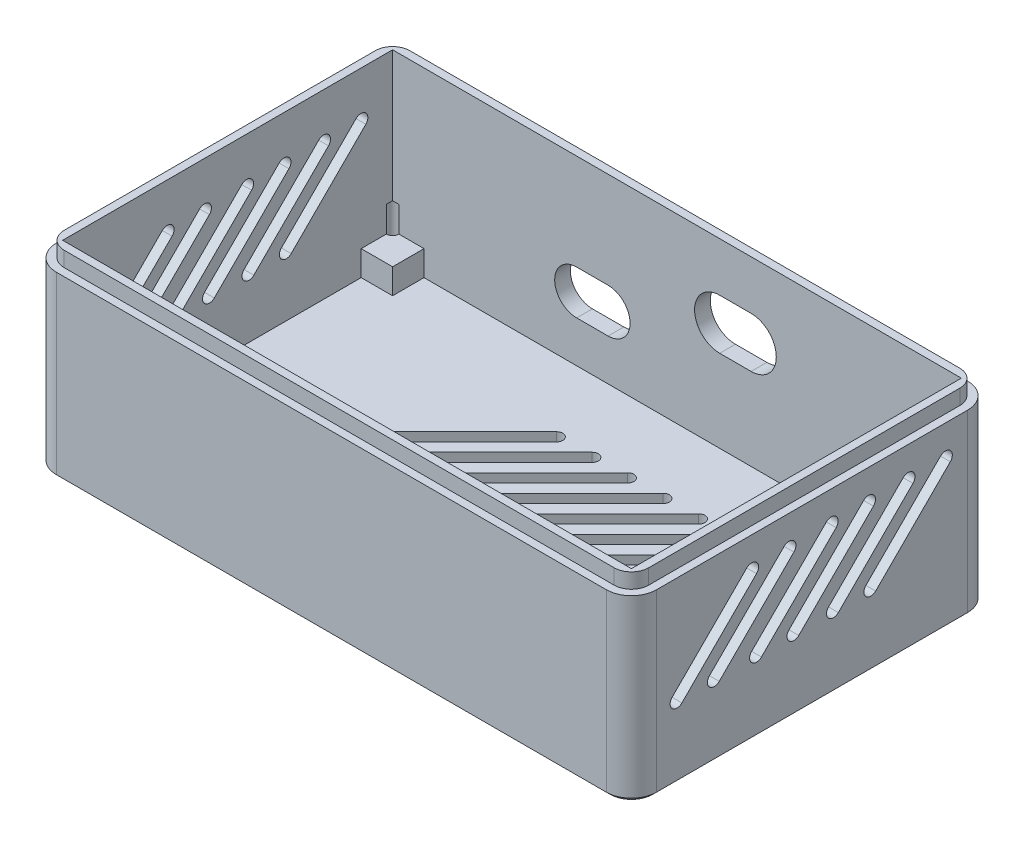
SolidWorks part; units mm, degrees
ref_plane "Front Plane" through (0, 0, 0) normal (0, 0, 1) x (1, 0, 0)
ref_plane "Top Plane" through (0, 0, 0) normal (0, 1, 0) x (1, 0, 0)
ref_plane "Right Plane" through (0, 0, 0) normal (1, 0, 0) x (0, 0, -1)
sketch "Croquis_contorno" plane through (0, 0, 0) normal (0, 1, 0) x (1, 0, 0)
  line L0 (-43.75, -28.75) -> (43.75, -28.75)
  line L1 (47.75, -24.75) -> (47.75, 24.75)
  line L2 (43.75, 28.75) -> (-43.75, 28.75)
  line L3 (-47.75, 24.75) -> (-47.75, -24.75)
  arc A0 (43.75, -28.75) -> (47.75, -24.75) centre (43.75, -24.75) ccw
  arc A1 (47.75, 24.75) -> (43.75, 28.75) centre (43.75, 24.75) ccw
  arc A2 (-43.75, 28.75) -> (-47.75, 24.75) centre (-43.75, 24.75) ccw
  arc A3 (-47.75, -24.75) -> (-43.75, -28.75) centre (-43.75, -24.75) ccw
  dimension "D3" = 4
  dimension "D1" = 95.5
  dimension "D2" = 57.5
extrude "Cuerpo" add sketch "Croquis_contorno" along normal blind 28.5
ref_plane "Plano_Top Plane_+28_5" through (0, 28.5, 0) normal (0, 1, 0) x (1, 0, 0)
sketch "Croquis_hueco_PCB" plane through (0, 28.5, 0) normal (0, 1, 0) x (1, 0, 0)
  line L1 (-45.25, -26.25) -> (45.25, -26.25)
  line L2 (-45.25, -26.25) -> (-45.25, 26.25)
  line L3 (-45.25, 26.25) -> (45.25, 26.25)
  line L4 (45.25, -26.25) -> (45.25, 26.25)
  line L5 (-45.25, -26.25) -> (45.25, 26.25) construction
  line L6 (-45.25, 26.25) -> (45.25, -26.25) construction
  dimension "D1" = 90.5
  dimension "D2" = 52.5
extrude "Hueco_PCB" cut sketch "Croquis_hueco_PCB" against normal blind 26.5
sketch "Croquis_labio" plane through (0, 28.5, 0) normal (0, 1, 0) x (1, 0, 0)
  line L0 (-43.75, -27.5) -> (43.75, -27.5)
  line L1 (46.5, -24.75) -> (46.5, 24.75)
  line L2 (43.75, 27.5) -> (-43.75, 27.5)
  line L3 (-46.5, 24.75) -> (-46.5, -24.75)
  line L5 (-45.25, -26.25) -> (45.25, -26.25)
  line L6 (-45.25, -26.25) -> (-45.25, 26.25)
  line L7 (-45.25, 26.25) -> (45.25, 26.25)
  line L8 (45.25, -26.25) -> (45.25, 26.25)
  line L9 (-45.25, -26.25) -> (45.25, 26.25) construction
  line L10 (-45.25, 26.25) -> (45.25, -26.25) construction
  arc A0 (43.75, -27.5) -> (46.5, -24.75) centre (43.75, -24.75) ccw
  arc A1 (46.5, 24.75) -> (43.75, 27.5) centre (43.75, 24.75) ccw
  arc A2 (-43.75, 27.5) -> (-46.5, 24.75) centre (-43.75, 24.75) ccw
  arc A3 (-46.5, -24.75) -> (-43.75, -27.5) centre (-43.75, -24.75) ccw
  point P12 (0, 0)
  dimension "D3" = 2.75
  dimension "D1" = 93
  dimension "D2" = 55
extrude "Labio_lip" add sketch "Croquis_labio" along normal blind 2.4
ref_plane "Plano_Top Plane_+2" through (0, 2, 0) normal (0, 1, 0) x (1, 0, 0)
sketch "Croquis_apoyos" plane through (0, 2, 0) normal (0, 1, 0) x (1, 0, 0)
  line L0 (45.25, 26.25) -> (-45.25, 26.25) construction
  line L1 (-45.25, -26.25) -> (-40.25, -26.25)
  line L2 (-45.25, -26.25) -> (-45.25, -21.25)
  line L3 (-45.25, -21.25) -> (-40.25, -21.25)
  line L4 (-40.25, -26.25) -> (-40.25, -21.25)
  line L5 (-45.25, -26.25) -> (-40.25, -21.25) construction
  line L6 (-45.25, -21.25) -> (-40.25, -26.25) construction
  line L7 (-45.25, 21.25) -> (-40.25, 21.25)
  line L8 (-45.25, 21.25) -> (-45.25, 26.25)
  line L9 (-45.25, 26.25) -> (-40.25, 26.25)
  line L10 (-40.25, 21.25) -> (-40.25, 26.25)
  line L11 (-45.25, 21.25) -> (-40.25, 26.25) construction
  line L12 (-45.25, 26.25) -> (-40.25, 21.25) construction
  line L13 (45.25, -26.25) -> (45.25, 26.25) construction
  line L14 (40.25, -26.25) -> (45.25, -26.25)
  line L15 (40.25, -26.25) -> (40.25, -21.25)
  line L16 (40.25, -21.25) -> (45.25, -21.25)
  line L17 (45.25, -26.25) -> (45.25, -21.25)
  line L18 (40.25, -26.25) -> (45.25, -21.25) construction
  line L19 (40.25, -21.25) -> (45.25, -26.25) construction
  line L21 (40.25, 21.25) -> (45.25, 21.25)
  line L22 (40.25, 21.25) -> (40.25, 26.25)
  line L23 (40.25, 26.25) -> (45.25, 26.25)
  line L24 (45.25, 21.25) -> (45.25, 26.25)
  line L25 (40.25, 21.25) -> (45.25, 26.25) construction
  line L26 (40.25, 26.25) -> (45.25, 21.25) construction
  point P0 (-42.75, 23.75)
  point P11 (42.75, -23.75)
  point P18 (42.75, 23.75)
  dimension "D1" = 5
  dimension "D2" = 5
extrude "Apoyos_PCB" add sketch "Croquis_apoyos" along normal blind 4
sketch "Croquis_alivios" plane through (0, 2, 0) normal (0, 1, 0) x (1, 0, 0)
  circle A0 centre (-45.25, -26.25) radius 1
  circle A1 centre (-45.25, 26.25) radius 1
  circle A2 centre (45.25, -26.25) radius 1
  circle A3 centre (45.25, 26.25) radius 1
  dimension "D1" = 2
extrude "Alivios_esquinas" cut sketch "Croquis_alivios" along normal blind 8.1
sketch "Croquis_salidas" plane through (0, 0, 0) normal (0, 0, 1) x (1, 0, 0)
  line L0 (6.8, 19.1) -> (11.8, 19.1) construction
  line L1 (6.8, 23.1) -> (11.8, 23.1)
  line L2 (6.8, 15.1) -> (11.8, 15.1)
  line L3 (-15.96, 12.1) -> (-10.96, 12.1) construction
  line L4 (-15.96, 15.6) -> (-10.96, 15.6)
  line L5 (-15.96, 8.6) -> (-10.96, 8.6)
  arc A0 (6.8, 23.1) -> (6.8, 15.1) centre (6.8, 19.1) ccw
  arc A1 (11.8, 15.1) -> (11.8, 23.1) centre (11.8, 19.1) ccw
  arc A2 (-15.96, 15.6) -> (-15.96, 8.6) centre (-15.96, 12.1) ccw
  arc A3 (-10.96, 8.6) -> (-10.96, 15.6) centre (-10.96, 12.1) ccw
  point P2 (9.3, 19.1)
  point P7 (-13.46, 12.1)
  point P14 (0, 0)
extrude "Salidas_USB_y_panel" cut sketch "Croquis_salidas" against normal through all
sketch "Croquis_ventilas" plane through (0, 0, 0) normal (1, 0, 0) x (0, 0, -1)
  line L0 (-21.496, 11.6603) -> (-9.6167, 23.5397) construction
  line L1 (-22.2739, 12.4381) -> (-10.3945, 24.3175)
  line L2 (-20.7182, 10.8825) -> (-8.8388, 22.7619)
  line L3 (-15.5563, 11.6603) -> (-3.677, 23.5397) construction
  line L4 (-16.3342, 12.4381) -> (-4.4548, 24.3175)
  line L5 (-14.7785, 10.8825) -> (-2.8991, 22.7619)
  line L6 (-8.8388, 11.6603) -> (3.0406, 23.5397) construction
  line L7 (-9.6167, 12.4381) -> (2.2627, 24.3175)
  line L8 (-8.061, 10.8825) -> (3.8184, 22.7619)
  line L9 (-2.8991, 11.6603) -> (8.9803, 23.5397) construction
  line L10 (-3.677, 12.4381) -> (8.2024, 24.3175)
  line L11 (-2.1213, 10.8825) -> (9.7581, 22.7619)
  line L12 (3.3941, 11.6603) -> (15.2735, 23.5397) construction
  line L13 (2.6163, 12.4381) -> (14.4957, 24.3175)
  line L14 (4.1719, 10.8825) -> (16.0513, 22.7619)
  line L15 (9.3338, 11.6603) -> (21.2132, 23.5397) construction
  line L16 (8.556, 12.4381) -> (20.4354, 24.3175)
  line L17 (10.1116, 10.8825) -> (21.991, 22.7619)
  arc A0 (-22.2739, 12.4381) -> (-20.7182, 10.8825) centre (-21.496, 11.6603) ccw
  arc A1 (-8.8388, 22.7619) -> (-10.3945, 24.3175) centre (-9.6167, 23.5397) ccw
  arc A2 (-16.3342, 12.4381) -> (-14.7785, 10.8825) centre (-15.5563, 11.6603) ccw
  arc A3 (-2.8991, 22.7619) -> (-4.4548, 24.3175) centre (-3.677, 23.5397) ccw
  arc A4 (-9.6167, 12.4381) -> (-8.061, 10.8825) centre (-8.8388, 11.6603) ccw
  arc A5 (3.8184, 22.7619) -> (2.2627, 24.3175) centre (3.0406, 23.5397) ccw
  arc A6 (-3.677, 12.4381) -> (-2.1213, 10.8825) centre (-2.8991, 11.6603) ccw
  arc A7 (9.7581, 22.7619) -> (8.2024, 24.3175) centre (8.9803, 23.5397) ccw
  arc A8 (2.6163, 12.4381) -> (4.1719, 10.8825) centre (3.3941, 11.6603) ccw
  arc A9 (16.0513, 22.7619) -> (14.4957, 24.3175) centre (15.2735, 23.5397) ccw
  arc A10 (8.556, 12.4381) -> (10.1116, 10.8825) centre (9.3338, 11.6603) ccw
  arc A11 (21.991, 22.7619) -> (20.4354, 24.3175) centre (21.2132, 23.5397) ccw
  point P2 (-15.5563, 17.6)
  point P7 (-9.6167, 17.6)
  point P14 (-2.8991, 17.6)
  point P21 (3.0406, 17.6)
  point P28 (9.3338, 17.6)
  point P35 (15.2735, 17.6)
  point P42 (0, 0)
extrude "Ventilas_laterales" cut sketch "Croquis_ventilas" along normal through all and the other way through all
sketch "Croquis_rejilla_piso" plane through (0, 0, 0) normal (0, 1, 0) x (1, 0, 0)
  line L0 (-37.4767, -14.8492) -> (-7.7782, 14.8492) construction
  line L1 (-38.1838, -14.1421) -> (-8.4853, 15.5563)
  line L2 (-36.7696, -15.5563) -> (-7.0711, 14.1421)
  line L3 (-31.8198, -14.8492) -> (-2.1213, 14.8492) construction
  line L4 (-32.5269, -14.1421) -> (-2.8284, 15.5563)
  line L5 (-31.1127, -15.5563) -> (-1.4142, 14.1421)
  line L6 (-26.163, -14.8492) -> (3.5355, 14.8492) construction
  line L7 (-26.8701, -14.1421) -> (2.8284, 15.5563)
  line L8 (-25.4558, -15.5563) -> (4.2426, 14.1421)
  line L9 (-20.5061, -14.8492) -> (9.1924, 14.8492) construction
  line L10 (-21.2132, -14.1421) -> (8.4853, 15.5563)
  line L11 (-19.799, -15.5563) -> (9.8995, 14.1421)
  line L12 (-14.8492, -14.8492) -> (14.8492, 14.8492) construction
  line L13 (-15.5563, -14.1421) -> (14.1421, 15.5563)
  line L14 (-14.1421, -15.5563) -> (15.5563, 14.1421)
  line L15 (-9.1924, -14.8492) -> (20.5061, 14.8492) construction
  line L16 (-9.8995, -14.1421) -> (19.799, 15.5563)
  line L17 (-8.4853, -15.5563) -> (21.2132, 14.1421)
  line L18 (-3.5355, -14.8492) -> (26.163, 14.8492) construction
  line L19 (-4.2426, -14.1421) -> (25.4558, 15.5563)
  line L20 (-2.8284, -15.5563) -> (26.8701, 14.1421)
  line L21 (2.1213, -14.8492) -> (31.8198, 14.8492) construction
  line L22 (1.4142, -14.1421) -> (31.1127, 15.5563)
  line L23 (2.8284, -15.5563) -> (32.5269, 14.1421)
  line L24 (7.7782, -14.8492) -> (37.4767, 14.8492) construction
  line L25 (7.0711, -14.1421) -> (36.7696, 15.5563)
  line L26 (8.4853, -15.5563) -> (38.1838, 14.1421)
  arc A0 (-38.1838, -14.1421) -> (-36.7696, -15.5563) centre (-37.4767, -14.8492) ccw
  arc A1 (-7.0711, 14.1421) -> (-8.4853, 15.5563) centre (-7.7782, 14.8492) ccw
  arc A2 (-32.5269, -14.1421) -> (-31.1127, -15.5563) centre (-31.8198, -14.8492) ccw
  arc A3 (-1.4142, 14.1421) -> (-2.8284, 15.5563) centre (-2.1213, 14.8492) ccw
  arc A4 (-26.8701, -14.1421) -> (-25.4558, -15.5563) centre (-26.163, -14.8492) ccw
  arc A5 (4.2426, 14.1421) -> (2.8284, 15.5563) centre (3.5355, 14.8492) ccw
  arc A6 (-21.2132, -14.1421) -> (-19.799, -15.5563) centre (-20.5061, -14.8492) ccw
  arc A7 (9.8995, 14.1421) -> (8.4853, 15.5563) centre (9.1924, 14.8492) ccw
  arc A8 (-15.5563, -14.1421) -> (-14.1421, -15.5563) centre (-14.8492, -14.8492) ccw
  arc A9 (15.5563, 14.1421) -> (14.1421, 15.5563) centre (14.8492, 14.8492) ccw
  arc A10 (-9.8995, -14.1421) -> (-8.4853, -15.5563) centre (-9.1924, -14.8492) ccw
  arc A11 (21.2132, 14.1421) -> (19.799, 15.5563) centre (20.5061, 14.8492) ccw
  arc A12 (-4.2426, -14.1421) -> (-2.8284, -15.5563) centre (-3.5355, -14.8492) ccw
  arc A13 (26.8701, 14.1421) -> (25.4558, 15.5563) centre (26.163, 14.8492) ccw
  arc A14 (1.4142, -14.1421) -> (2.8284, -15.5563) centre (2.1213, -14.8492) ccw
  arc A15 (32.5269, 14.1421) -> (31.1127, 15.5563) centre (31.8198, 14.8492) ccw
  arc A16 (7.0711, -14.1421) -> (8.4853, -15.5563) centre (7.7782, -14.8492) ccw
  arc A17 (38.1838, 14.1421) -> (36.7696, 15.5563) centre (37.4767, 14.8492) ccw
  point P2 (-22.6274, 0)
  point P7 (-16.9706, 0)
  point P14 (-11.3137, 0)
  point P21 (-5.6569, 0)
  point P28 (0, 0)
  point P35 (5.6569, 0)
  point P42 (11.3137, 0)
  point P49 (16.9706, 0)
  point P56 (22.6274, 0)
  point P63 (0, 0)
extrude "Rejilla_piso" cut sketch "Croquis_rejilla_piso" along normal blind 2
chamfer "Chaflan_base" distance 0.6 angle 45 8 edges at (0, 0, 28.75) (46.5784, 0, 27.5784) (47.75, 0, 0) (46.5784, 0, -27.5784) (0, 0, -28.75) (-46.5784, 0, -27.5784) (-47.75, 0, 0) (-46.5784, 0, 27.5784) tangent propagation no
